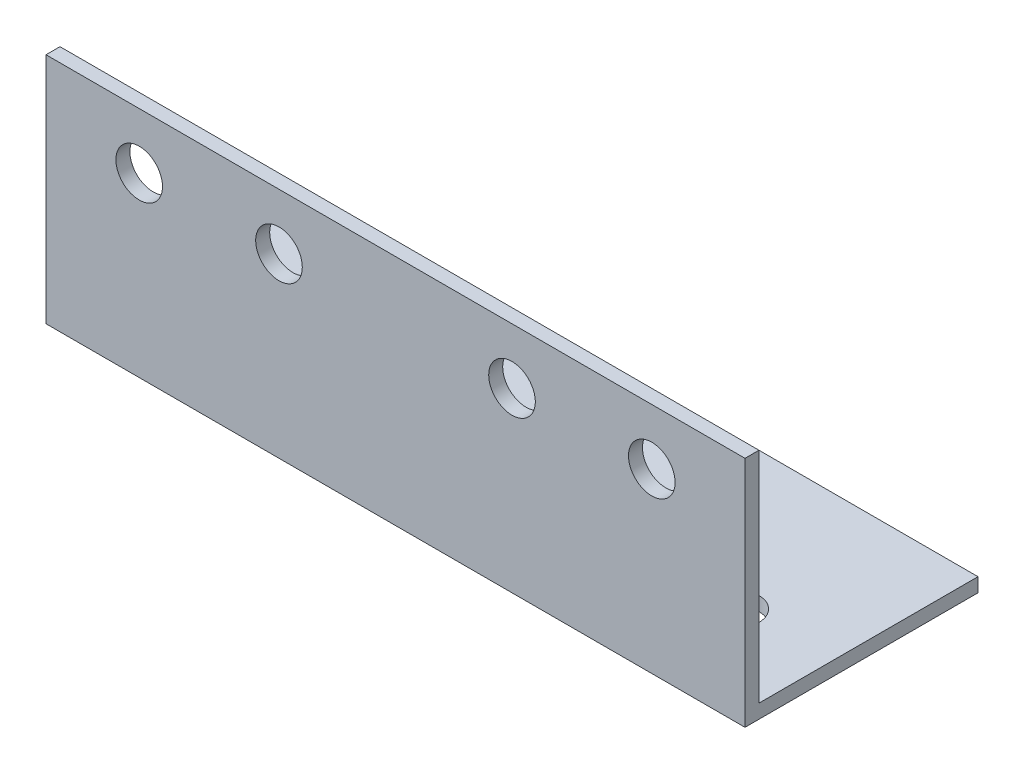
SolidWorks part; units mm, degrees
ref_plane "Спереди" through (0, 0, 0) normal (0, 0, 1) x (1, 0, 0)
ref_plane "Сверху" through (0, 0, 0) normal (0, 1, 0) x (1, 0, 0)
ref_plane "Справа" through (0, 0, 0) normal (1, 0, 0) x (0, 0, -1)
sketch "Эскиз1" plane through (0, 0, 0) normal (1, 0, 0) x (0, 0, -1)
  line L0 (0, 0) -> (0, 50)
  line L1 (0, 0) -> (50, 0)
extrude "Вытянуть-Тонкостенный1" add sketch "Эскиз1" along normal blind 150 thin thin type one direction reverse wall 3
sketch "Эскиз2" plane through (0, 0, 0) normal (0, 0, 1) x (1, 0, 0)
  line L0 (75, 57.1198) -> (75, 24.9932) construction
  circle A0 centre (20, 38) radius 5
  circle A1 centre (50, 38) radius 5
  circle A2 centre (100, 38) radius 5
  circle A3 centre (130, 38) radius 5
  dimension "D1" = 2
extrude "Вырез-Вытянуть1" cut sketch "Эскиз2" against normal through all
sketch "Эскиз3" plane through (0, 0, 0) normal (0, -1, 0) x (1, 0, 0)
  line L0 (75, -55.6806) -> (75, -1.3862) construction
  circle A0 centre (130, -18) radius 5
  circle A1 centre (100, -18) radius 5
  circle A2 centre (50, -18) radius 5
  circle A3 centre (20, -18) radius 5
  dimension "D1" = 2
extrude "Вырез-Вытянуть2" cut sketch "Эскиз3" against normal through all
